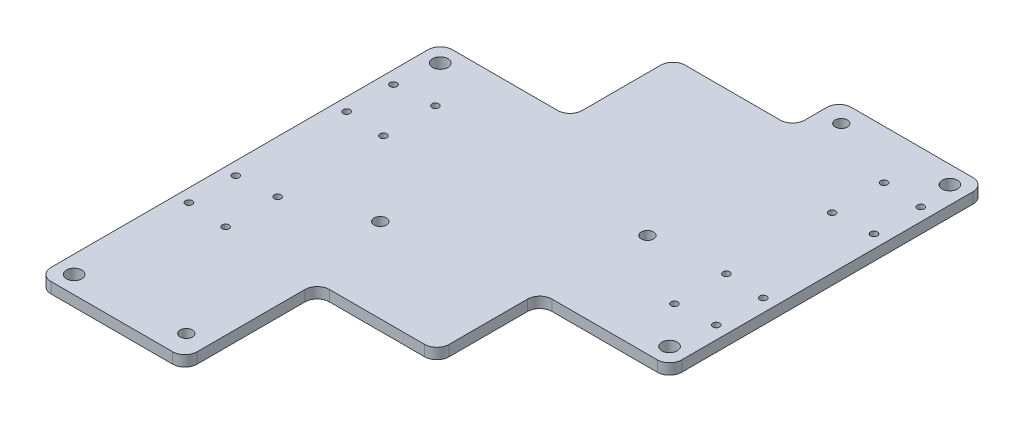
SolidWorks part; units mm, degrees
note: The reader was unsure of these and kept them because the rebuilt part matched: thickness of "Base-Flange1", "Sheet-Metal3", "Sheet-Metal5".
ref_plane "Front" through (0, 0, 0) normal (0, 0, 1) x (1, 0, 0)
ref_plane "Top" through (0, 0, 0) normal (0, 1, 0) x (1, 0, 0)
ref_plane "Right" through (0, 0, 0) normal (1, 0, 0) x (0, 0, -1)
sketch "Sketch1" plane through (0, 0, 0) normal (0, 1, 0) x (1, 0, 0)
  line L0 (-102.4883, 43.0594) -> (-102.4883, -165.0379)
  line L5 (-105.6633, -19.05) -> (-105.6633, -16.51) construction
  line L6 (-31.2457, 96.4382) -> (22.7543, 96.4382) construction
  line L7 (-46.1643, -165.0379) -> (-30.7501, -165.0379) construction
  line L8 (-102.4883, -165.0379) -> (-26.7501, -165.0379)
  line L9 (-26.7501, -165.0379) -> (-26.7501, -96.4382)
  line L10 (-26.7501, -161.0379) -> (-26.7501, -100.4382) construction
  line L16 (-102.4883, 43.0594) -> (-35.2457, 43.0594)
  line L17 (-35.2457, 43.0594) -> (-35.2457, 96.4382)
  line L18 (-35.2457, 96.4382) -> (26.7543, 96.4382)
  line L19 (26.7543, 100.4382) -> (26.7543, 116.5825) construction
  line L20 (-35.2457, 71.0688) -> (-35.2457, 92.4382) construction
  line L22 (26.7543, 96.4382) -> (26.7543, 120.5825)
  line L24 (26.7543, 120.5825) -> (102.4883, 120.5825)
  line L25 (102.4883, 120.5825) -> (102.4883, -43.0594)
  line L26 (46.1643, 120.5825) -> (30.7543, 120.5825) construction
  line L27 (-89.0263, 19.05) -> (-89.0263, 43.0594) construction
  line L28 (-72.3893, 19.05) -> (-105.6633, 19.05) construction
  line L29 (-35.2457, 43.0594) -> (-4.2478, 43.0594) construction
  line L30 (-4.2478, 43.0594) -> (-4.2478, 67.0688) construction
  line L32 (31.2457, -67.0688) -> (-22.7543, -67.0688) construction
  line L33 (105.6633, 19.05) -> (105.6633, 16.51) construction
  line L34 (-26.7501, -96.4382) -> (35.2457, -96.4382)
  line L35 (35.2457, -96.4382) -> (35.2457, -43.0594)
  line L36 (35.2457, -43.0594) -> (102.4883, -43.0594)
  line L37 (4.2457, -67.0688) -> (4.2457, -43.0594) construction
  line L39 (4.2457, -43.0594) -> (35.2457, -43.0594) construction
  line L40 (89.0263, -19.05) -> (89.0263, -43.0594) construction
  line L41 (72.3893, -19.05) -> (105.6633, -19.05) construction
  line L42 (-31.2457, 67.0688) -> (22.7501, 67.0688) construction
  line L43 (31.2457, -96.4382) -> (-22.7501, -96.4382) construction
  line L44 (35.2457, -92.4382) -> (35.2457, -71.0688) construction
  circle A0 centre (-37.7543, -153.3052) radius 3.175
  circle A1 centre (-37.7543, -153.3052) radius 3.175 construction
  circle A2 centre (-37.7543, -52.769) radius 3.175
  circle A3 centre (37.7543, 10.2018) radius 3.175
  circle A4 centre (37.7543, 110.7379) radius 3.175
  circle A5 centre (95.8141, 93.8887) radius 1.778
  circle A6 centre (75.4289, 95.2239) radius 1.778
  circle A7 centre (75.4289, 68.2831) radius 1.778
  circle A8 centre (95.8141, 69.6183) radius 1.778
  circle A9 centre (95.8141, 12.1352) radius 1.778
  circle A10 centre (95.8141, -12.1352) radius 1.778
  circle A11 centre (75.4289, 13.4704) radius 1.778
  circle A12 centre (75.4289, -13.4704) radius 1.778
  circle A13 centre (-95.8141, 12.1352) radius 1.778
  circle A14 centre (-75.4289, 13.4704) radius 1.778
  circle A15 centre (-75.4289, -13.4704) radius 1.778
  circle A16 centre (-95.8141, -12.1352) radius 1.778
  circle A17 centre (-95.8141, -69.6183) radius 1.778
  circle A18 centre (-75.4289, -68.2831) radius 1.778
  circle A19 centre (-75.4289, -95.2239) radius 1.778
  circle A20 centre (-95.8141, -93.8887) radius 1.778
  arc A21 (-73.6509, -95.2239) -> (-77.2069, -95.2239) centre (-75.4289, -95.2239) ccw construction
  point P16 (0, 0.5475)
  point P20 (-89.0263, 19.05)
  point P22 (0, 0)
  point P31 (4.2457, -67.0688)
  point P34 (0, 0)
  point P115 (0, 0)
  point P116 (0, 0)
  point P117 (-4.2478, 67.0688)
  dimension "D1" = 3.175
  dimension "D2" = 3.175
base flange "Base-Flange1" sketch "Sketch1" thickness 5.588 reverse thickness direction no parameters "D1"=3
fillet "Fillet1" radius 6.35 12 edges at (-26.7501, -2.794, 165.0379) (-102.4883, -2.794, -43.0594) (-102.4883, -2.794, 165.0379) (-26.7501, -2.794, 96.4382) (35.2457, -2.794, 96.4382) (35.2457, -2.794, 43.0594) (102.4883, -2.794, 43.0594) (102.4883, -2.794, -120.5825) (26.7543, -2.794, -120.5825) (26.7543, -2.794, -96.4382) (-35.2457, -2.794, -96.4382) (-35.2457, -2.794, -43.0594)
sketch "Sketch3" plane through (0, 0, 0) normal (0, 1, 0) x (1, 0, 0)
  line L0 (-102.4883, 33.903) -> (-93.332, 33.903) construction
  line L1 (-102.4883, 36.7094) -> (-102.4883, -158.6879) construction
  line L2 (-93.332, 33.903) -> (-93.332, 43.0594) construction
  line L3 (-41.5957, 43.0594) -> (-96.1383, 43.0594) construction
  line L4 (-102.4883, -60.9893) -> (35.2457, -60.9893) construction
  line L5 (35.2457, -90.0882) -> (35.2457, -49.4094) construction
  line L6 (-93.332, -155.8816) -> (-93.332, -165.0379) construction
  line L7 (-102.4883, -155.8816) -> (-93.332, -155.8816) construction
  line L8 (0, 0) -> (0, -96.4382) construction
  line L9 (-20.4001, -96.4382) -> (28.8957, -96.4382) construction
  line L10 (93.332, 111.4262) -> (93.332, 120.5825) construction
  line L11 (96.1383, 120.5825) -> (33.1043, 120.5825) construction
  line L12 (93.332, 111.4262) -> (102.4883, 111.4262) construction
  line L13 (102.4883, -36.7094) -> (102.4883, 114.2325) construction
  line L14 (102.4883, 38.7616) -> (-35.2457, 38.7616) construction
  line L15 (-35.2457, 90.0882) -> (-35.2457, 49.4094) construction
  line L16 (93.332, -33.903) -> (102.4883, -33.903) construction
  line L17 (93.332, -33.903) -> (93.332, -43.0594) construction
  circle A4 centre (-93.332, 33.903) radius 3.9687
  arc A10 (-96.1383, 43.0594) -> (-102.4883, 36.7094) centre (-96.1383, 36.7094) ccw construction
  circle A11 centre (-93.332, -155.8816) radius 3.9687
  circle A14 centre (93.332, 111.4262) radius 3.9687
  arc A16 (102.4883, 114.2325) -> (96.1383, 120.5825) centre (96.1383, 114.2325) ccw construction
  circle A17 centre (93.332, -33.903) radius 3.9687
  dimension "D1" = 6.35
  dimension "D2" = 7.9375
  dimension "D3" = 6.35
  dimension "D4" = 7.9375
extrude "Cut-Extrude2" cut sketch "Sketch3" against normal up to next normal cut yes
sketch "Bend-Lines1" [suppressed] plane through (0, 0, 0) normal (0, 1, 0) x (1, 0, 0)
sketch "Bounding-Box1" [suppressed] plane through (0, 0, 0) normal (0, 1, 0) x (1, 0, 0)
sheet metal parameters "Sheet-Metal3" thickness 5.588 parameters "D1"=3
flat pattern "Flat-Pattern3" [suppressed]
sketch "Bend-Lines2" plane through (0, 0, 0) normal (0, 1, 0) x (1, 0, 0)
sketch3d "Bounding-Box2" [suppressed]
  line L0 (115.1883, 120.5825, 0) -> (115.1883, -165.038, 0) construction
  line L1 (-115.1883, 120.5825, 0) -> (-115.1883, -165.0379, 0) construction
  line L2 (115.1883, 120.5825, 0) -> (-115.1883, 120.5825, 0) construction
  line L3 (115.1883, -165.038, 0) -> (-115.1883, -165.0379, 0) construction
sheet metal parameters "Sheet-Metal5" thickness 5.588 parameters "D1"=3, "D7"=4.7625
flat pattern "Flat-Pattern3"
sketch "Bend-Lines2" plane through (0, 0, 0) normal (0, 1, 0) x (1, 0, 0)
sketch3d "Bounding-Box2" [suppressed]
  line L0 (102.4883, 120.5825, 0) -> (102.4883, -165.038, 0) construction
  line L1 (-102.4883, 120.5825, 0) -> (-102.4883, -165.0379, 0) construction
  line L2 (102.4883, 120.5825, 0) -> (-102.4883, 120.5825, 0) construction
  line L3 (102.4883, -165.038, 0) -> (-102.4883, -165.0379, 0) construction
